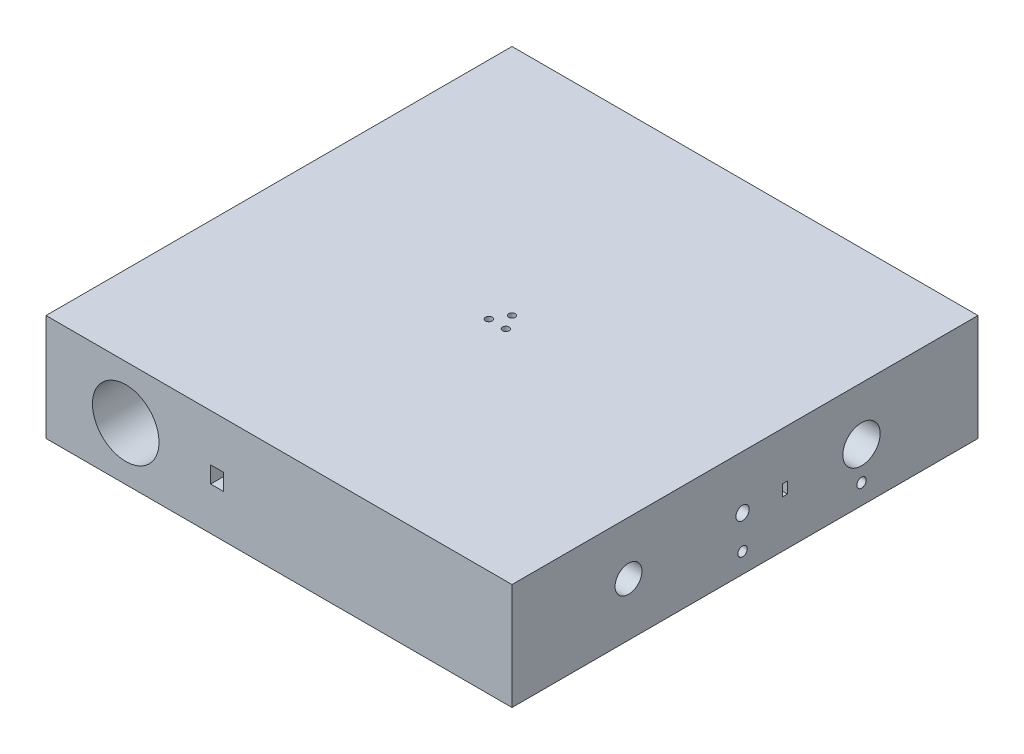
SolidWorks part; units mm, degrees
ref_plane "Front Plane" through (0, 0, 0) normal (0, 0, 1) x (1, 0, 0)
ref_plane "Top Plane" through (0, 0, 0) normal (0, 1, 0) x (1, 0, 0)
ref_plane "Right Plane" through (0, 0, 0) normal (1, 0, 0) x (0, 0, -1)
sketch "Sketch1" plane through (0, 0, 0) normal (0, 1, 0) x (1, 0, 0)
  line L1 (-175, 175) -> (175, 175)
  line L2 (-175, 175) -> (-175, -175)
  line L3 (-175, -175) -> (175, -175)
  line L4 (175, 175) -> (175, -175)
  line L5 (-175, 175) -> (175, -175) construction
  line L6 (-175, -175) -> (175, 175) construction
  point P0 (0, 0)
  dimension "D1" = 350
  dimension "D2" = 350
extrude "Boss-Extrude1" add sketch "Sketch1" along normal blind 80
sketch "Sketch2" plane through (0, 80, 0) normal (0, 1, 0) x (1, 0, 0)
  line L0 (0, 0) -> (0, 175)
  line L1 (175, 175) -> (-175, 175) construction
  line L2 (175, -175) -> (175, 175) construction
  line L3 (-175, 175) -> (-175, -175) construction
  circle A0 centre (0, 0) radius 2.5
  circle A1 centre (6.4, -11.0274) radius 2.5
  circle A2 centre (-6.4, -11.0274) radius 2.5
  point P7 (175, 0)
  dimension "D1" = 5
  dimension "D5" = 5
  dimension "D6" = 5
  dimension "D9" = 168.6
  dimension "D2" = 175
  dimension "D3" = 175
  dimension "D4" = 12.75
  dimension "D7" = 12.75
  dimension "D8" = 168.6
extrude "Cut-Extrude1" cut sketch "Sketch2" against normal through all contours A0 region at (-1.7178, 80, 1.7178)
extrude "Cut-Extrude2" cut sketch "Sketch2<4>" against normal through all contours A1 region at (6.4, 80, 11.0274)
sketch "Sketch2<4>" plane through (0, 80, 0) normal (0, 1, 0) x (1, 0, 0) same geometry as "Sketch2"
extrude "Cut-Extrude3" cut sketch "Sketch2<5>" against normal through all contours A2 region at (-6.4, 80, 11.0274)
sketch "Sketch2<5>" plane through (0, 80, 0) normal (0, 1, 0) x (1, 0, 0) same geometry as "Sketch2"
sketch "Sketch3" plane through (-175, 0, 0) normal (-1, 0, 0) x (0, 0, 1)
  line L0 (-175, 80) -> (-175, 0) construction
  line L1 (-28.15, 35.4316) -> (-31.85, 35.4316)
  line L2 (-28.15, 35.4316) -> (-28.15, 43.9316)
  line L3 (-28.15, 43.9316) -> (-31.85, 43.9316)
  line L4 (-31.85, 35.4316) -> (-31.85, 43.9316)
  line L5 (-28.15, 35.4316) -> (-31.85, 43.9316) construction
  line L6 (-28.15, 43.9316) -> (-31.85, 35.4316) construction
  point P0 (-30, 39.6816)
  point P7 (-175, 40)
  dimension "D1" = 8.5
  dimension "D2" = 3.7
  dimension "D3" = 145
extrude "Cut-Extrude4" cut sketch "Sketch3" against normal through all
sketch "Sketch4" plane through (-175, 0, 0) normal (-1, 0, 0) x (0, 0, 1)
  line L0 (175, 80) -> (175, 0) construction
  line L3 (-175, 0) -> (175, 0) construction
  circle A0 centre (87.5, 40) radius 10.1
  dimension "D1" = 20.2
  dimension "D2" = 87.5
  dimension "D3" = 40
extrude "Cut-Extrude5" cut sketch "Sketch4" against normal through all
sketch "Sketch6" plane through (-175, 0, 0) normal (-1, 0, 0) x (0, 0, 1)
  line L0 (-28.15, 35.4316) -> (-28.15, 43.9316) construction
  line L1 (-175, 0) -> (175, 0) construction
  circle A0 centre (1.85, 15) radius 3.555
  point P5 (-28.15, 39.6816)
  dimension "D1" = 7.11
  dimension "D2" = 30
  dimension "D3" = 15
extrude "Cut-Extrude7" cut sketch "Sketch6" against normal through all and the other way blind 10
sketch "Sketch7" plane through (-175, 0, 0) normal (-1, 0, 0) x (0, 0, 1)
  line L0 (-175, 80) -> (-175, 0) construction
  line L1 (-175, 0) -> (175, 0) construction
  circle A0 centre (-87.5, 15) radius 3.555
  dimension "D1" = 7.11
  dimension "D2" = 87.5
  dimension "D3" = 15
extrude "Cut-Extrude8" cut sketch "Sketch7" against normal through all
sketch "Sketch9" plane through (-175, 0, 0) normal (-1, 0, 0) x (0, 0, 1)
  line L0 (-175, 80) -> (-175, 0) construction
  line L1 (-175, 0) -> (175, 0) construction
  circle A0 centre (-87.5, 40) radius 14
  dimension "D1" = 28
  dimension "D2" = 87.5
  dimension "D3" = 40
extrude "Cut-Extrude10" cut sketch "Sketch9" against normal through all
sketch "Sketch11" plane through (-175, 0, 0) normal (-1, 0, 0) x (0, 0, 1)
  line L3 (-28.15, 35.4316) -> (-28.15, 43.9316) construction
  line L4 (-175, 0) -> (175, 0) construction
  circle A0 centre (1.85, 40) radius 5.025
  dimension "D1" = 10.05
  dimension "D2" = 30
  dimension "D3" = 40
extrude "Cut-Extrude12" cut sketch "Sketch11" against normal through all
sketch "Sketch13" plane through (0, 0, -175) normal (0, 0, -1) x (-1, 0, 0)
  line L0 (-175, 0) -> (175, 0) construction
  circle A0 centre (115.112, 40) radius 25
  dimension "D1" = 50
  dimension "D2" = 40
extrude "Cut-Extrude14" cut sketch "Sketch13" against normal through all
sketch "Sketch14" plane through (0, 0, -175) normal (0, 0, -1) x (-1, 0, 0)
  line L1 (51.3298, 32.1941) -> (41.6298, 32.1941)
  line L2 (51.3298, 32.1941) -> (51.3298, 44.6941)
  line L3 (51.3298, 44.6941) -> (41.6298, 44.6941)
  line L4 (41.6298, 32.1941) -> (41.6298, 44.6941)
  line L5 (51.3298, 32.1941) -> (41.6298, 44.6941) construction
  line L6 (51.3298, 44.6941) -> (41.6298, 32.1941) construction
  point P0 (46.4798, 38.4441)
  dimension "D1" = 9.7
  dimension "D2" = 12.5
extrude "Cut-Extrude18" cut sketch "Sketch14" against normal through all
